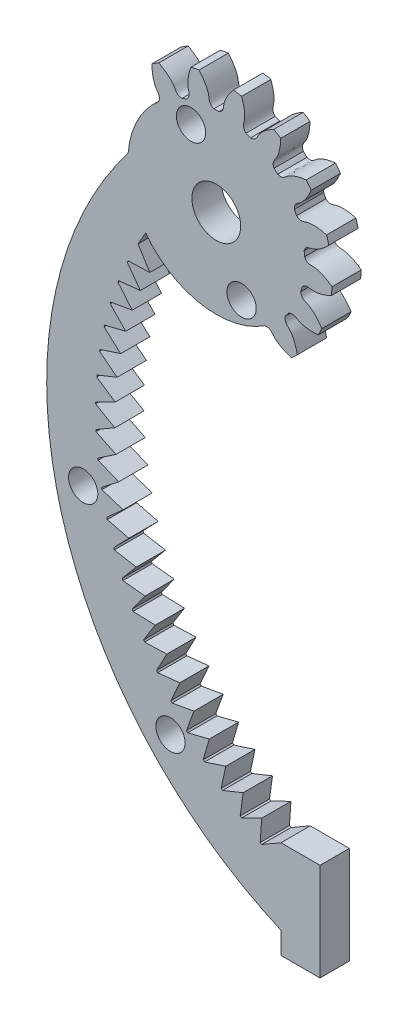
SolidWorks part; units mm, degrees
ref_plane "前视基准面" through (0, 0, 0) normal (0, 0, 1) x (1, 0, 0)
ref_plane "上视基准面" through (0, 0, 0) normal (0, 1, 0) x (1, 0, 0)
ref_plane "右视基准面" through (0, 0, 0) normal (1, 0, 0) x (0, 0, -1)
sketch "草图1" plane through (0, 0, 0) normal (0, 0, 1) x (1, 0, 0)
  circle A0 centre (0, 0) radius 11.875
extrude "凸台-拉伸1" add sketch "草图1" along normal blind 30
ref_axis "基准轴1" through (0, 0, -1.5) along (0, 0, 1)
sketch "草图2" plane through (0, 0, 0) normal (0, 0, 1) x (1, 0, 0)
  line L0 (0, 0) -> (0, 11.875) construction
  circle A0 centre (0, 0) radius 11.875 construction
  arc A1 (0.2521, 9.059) -> (-0.2521, 9.059) centre (0, 0) ccw
  arc A2 (3.8946, 13.4259) -> (-3.8946, 13.4259) centre (0, 0) ccw
  spline S0 degree 3 poles (0.2521, 9.059) (0.7848, 9.281) (0.7077, 9.6935) (0.7979, 10.081) (0.8062, 10.1139) (0.8163, 10.1505) (0.8282, 10.1907) (0.8421, 10.2345) (0.8582, 10.2818) (0.8766, 10.3324) (0.8974, 10.3865) (0.9208, 10.4438) (0.947, 10.5043) (0.976, 10.5679) (1.008, 10.6345) (1.0431, 10.704) (1.0815, 10.7763) (1.1232, 10.8513) (1.1685, 10.929) (1.2174, 11.0091) (1.27, 11.0916) (1.3265, 11.1763) (1.3869, 11.2632) (1.4514, 11.3521) (1.5201, 11.4429) (1.5931, 11.5354) (1.6704, 11.6295) (1.7522, 11.7251) (1.8386, 11.822) (1.9295, 11.9201) (2.0252, 12.0192) (2.1257, 12.1193) (2.2311, 12.22) (2.3414, 12.3213) (2.4567, 12.4231) (2.577, 12.5251) (2.7025, 12.6272) (2.8331, 12.7292) (2.969, 12.831) (3.1101, 12.9323) (3.2564, 13.0331) (3.4081, 13.1332) (3.6198, 13.2668) (3.7832, 13.3632) (3.8946, 13.4259) knots 0 0 0 0 0.193883 0.199024 0.204851 0.211363 0.21856 0.226443 0.235011 0.244265 0.254205 0.264829 0.27614 0.288136 0.300817 0.314184 0.328236 0.342973 0.358397 0.374505 0.391299 0.408779 0.426944 0.445795 0.465331 0.485552 0.506459 0.528051 0.550329 0.573293 0.596941 0.621276 0.646296 0.672001 0.698392 0.725468 0.753229 0.781677 0.810809 0.840627 0.871131 0.90232 0.934195 1 1 1 1
  spline S1 degree 3 poles (-0.2521, 9.059) (-0.7848, 9.281) (-0.7077, 9.6935) (-0.7979, 10.081) (-0.8062, 10.1139) (-0.8163, 10.1505) (-0.8282, 10.1907) (-0.8421, 10.2345) (-0.8582, 10.2818) (-0.8766, 10.3324) (-0.8974, 10.3865) (-0.9208, 10.4438) (-0.947, 10.5043) (-0.976, 10.5679) (-1.008, 10.6345) (-1.0431, 10.704) (-1.0815, 10.7763) (-1.1232, 10.8513) (-1.1685, 10.929) (-1.2174, 11.0091) (-1.27, 11.0916) (-1.3265, 11.1763) (-1.3869, 11.2632) (-1.4514, 11.3521) (-1.5201, 11.4429) (-1.5931, 11.5354) (-1.6704, 11.6295) (-1.7522, 11.7251) (-1.8386, 11.822) (-1.9295, 11.9201) (-2.0252, 12.0192) (-2.1257, 12.1193) (-2.2311, 12.22) (-2.3414, 12.3213) (-2.4567, 12.4231) (-2.577, 12.5251) (-2.7025, 12.6272) (-2.8331, 12.7292) (-2.969, 12.831) (-3.1101, 12.9323) (-3.2564, 13.0331) (-3.4081, 13.1332) (-3.6198, 13.2668) (-3.7832, 13.3632) (-3.8946, 13.4259) knots 0 0 0 0 0.193883 0.199024 0.204851 0.211363 0.21856 0.226443 0.235011 0.244265 0.254205 0.264829 0.27614 0.288136 0.300817 0.314184 0.328236 0.342973 0.358397 0.374505 0.391299 0.408779 0.426944 0.445795 0.465331 0.485552 0.506459 0.528051 0.550329 0.573293 0.596941 0.621276 0.646296 0.672001 0.698392 0.725468 0.753229 0.781677 0.810809 0.840627 0.871131 0.90232 0.934195 1 1 1 1
extrude "切除-拉伸1" cut sketch "草图2" along normal through all
pattern_circular "阵列(圆周)1" count 17 every 21.176 about axis through (0, 0, -1.5) along (0, 0, 1) of "切除-拉伸1"
sketch "草图3" plane through (0, 0, 0) normal (0, 0, 1) x (1, 0, 0)
  circle A0 centre (0, 0) radius 10.625 construction
  dimension "Dn" = 21.25
sketch "草图4" plane through (0, 0, 0) normal (0, 1, 0) x (1, 0, 0)
  line L1 (-19.5079, 27) -> (19.5079, 27)
  line L2 (-19.5079, 27) -> (-19.5079, -27)
  line L3 (-19.5079, -27) -> (19.5079, -27)
  line L4 (19.5079, 27) -> (19.5079, -27)
  line L5 (-19.5079, 27) -> (19.5079, -27) construction
  line L6 (-19.5079, -27) -> (19.5079, 27) construction
  point P0 (0, 0)
  dimension "D1" = 3
extrude "切除-拉伸2" cut sketch "草图4" against normal through all both and the other way through all
sketch "草图5" plane through (0, 0, 27) normal (0, 0, -1) x (-1, 0, 0)
  circle A1 centre (0, 0) radius 2.5
  circle A3 centre (-2.5889, -6.5037) radius 1.5
  circle A5 centre (2.5889, 6.5037) radius 1.5
extrude "切除-拉伸3" cut sketch "草图5" against normal blind 10
sketch "草图6" plane through (0, 0, 27) normal (0, 0, -1) x (-1, 0, 0)
  arc A0 (-4.5546, -7.8348) -> (6.2893, 6.5248) centre (0, 0) ccw
  arc A34 (-1.9124, -8.8584) -> (-1.4168, -8.9511) centre (0, 0) ccw
  arc A35 (-0.4197, -11.8676) -> (0.4197, -11.8676) centre (0, 0) ccw
  arc A36 (1.4168, -8.9511) -> (1.9124, -8.8584) centre (0, 0) ccw
  arc A37 (3.8958, -11.2178) -> (4.6784, -10.9146) centre (0, 0) ccw
  arc A38 (4.5546, -7.8348) -> (4.9833, -7.5694) centre (0, 0) ccw
  arc A39 (7.685, -9.053) -> (8.3053, -8.4875) centre (0, 0) ccw
  arc A40 (7.0773, -5.6605) -> (7.3812, -5.2581) centre (0, 0) ccw
  arc A41 (10.4364, -5.6655) -> (10.8105, -4.9142) centre (0, 0) ccw
  arc A42 (8.6442, -2.7216) -> (8.7822, -2.2366) centre (0, 0) ccw
  arc A43 (11.7782, -1.5129) -> (11.8557, -0.6771) centre (0, 0) ccw
  arc A44 (9.0436, 0.5848) -> (8.9971, 1.0869) centre (0, 0) ccw
  arc A45 (11.5294, 2.8441) -> (11.2997, 3.6513) centre (0, 0) ccw
  arc A46 (8.2217, 3.8123) -> (7.9969, 4.2636) centre (0, 0) ccw
  arc A47 (9.7234, 6.8169) -> (9.2176, 7.4867) centre (0, 0) ccw
  arc A48 (6.2893, 6.5248) -> (5.9167, 6.8645) centre (0, 0) ccw
  arc A49 (6.6043, 9.8691) -> (5.8907, 10.3109) centre (0, 0) ccw
  arc A50 (3.5076, 8.3562) -> (3.0374, 8.5383) centre (0, 0) ccw
  arc A51 (2.5932, 11.5884) -> (1.7682, 11.7426) centre (0, 0) ccw
  arc A52 (0.2521, 9.059) -> (-0.2521, 9.059) centre (0, 0) ccw
  arc A53 (-1.7682, 11.7426) -> (-2.5932, 11.5884) centre (0, 0) ccw
  arc A54 (-3.0374, 8.5383) -> (-3.5076, 8.3562) centre (0, 0) ccw
  arc A55 (-5.8907, 10.3109) -> (-6.6043, 9.8691) centre (0, 0) ccw
  arc A56 (-5.9167, 6.8645) -> (-6.2893, 6.5248) centre (0, 0) ccw
  arc A57 (-9.2176, 7.4867) -> (-9.7234, 6.8169) centre (0, 0) ccw
  arc A58 (-7.9969, 4.2636) -> (-8.2217, 3.8123) centre (0, 0) ccw
  arc A59 (-11.2997, 3.6513) -> (-11.5294, 2.8441) centre (0, 0) ccw
  arc A60 (-8.9971, 1.0869) -> (-9.0436, 0.5848) centre (0, 0) ccw
  arc A61 (-11.8557, -0.6771) -> (-11.7782, -1.5129) centre (0, 0) ccw
  arc A62 (-8.7822, -2.2366) -> (-8.6442, -2.7216) centre (0, 0) ccw
  arc A63 (-10.8105, -4.9142) -> (-10.4364, -5.6655) centre (0, 0) ccw
  arc A64 (-7.3812, -5.2581) -> (-7.0773, -5.6605) centre (0, 0) ccw
  arc A65 (-8.3053, -8.4875) -> (-7.685, -9.053) centre (0, 0) ccw
  arc A66 (-4.9833, -7.5694) -> (-4.5546, -7.8348) centre (0, 0) ccw
  arc A67 (-4.6784, -10.9146) -> (-3.8958, -11.2178) centre (0, 0) ccw
  arc A68 (-1.9124, -8.8584) -> (-1.4168, -8.9511) centre (0, 0) ccw
  arc A69 (-0.4197, -11.8676) -> (0.4197, -11.8676) centre (0, 0) ccw
  arc A70 (1.4168, -8.9511) -> (1.9124, -8.8584) centre (0, 0) ccw
  arc A71 (3.8958, -11.2178) -> (4.6784, -10.9146) centre (0, 0) ccw
  arc A72 (4.5546, -7.8348) -> (4.9833, -7.5694) centre (0, 0) ccw
  arc A73 (7.685, -9.053) -> (8.3053, -8.4875) centre (0, 0) ccw
  arc A74 (7.0773, -5.6605) -> (7.3812, -5.2581) centre (0, 0) ccw
  arc A75 (10.4364, -5.6655) -> (10.8105, -4.9142) centre (0, 0) ccw
  arc A76 (8.6442, -2.7216) -> (8.7822, -2.2366) centre (0, 0) ccw
  arc A77 (11.7782, -1.5129) -> (11.8557, -0.6771) centre (0, 0) ccw
  arc A78 (9.0436, 0.5848) -> (8.9971, 1.0869) centre (0, 0) ccw
  arc A79 (11.5294, 2.8441) -> (11.2997, 3.6513) centre (0, 0) ccw
  arc A80 (8.2217, 3.8123) -> (7.9969, 4.2636) centre (0, 0) ccw
  arc A81 (9.7234, 6.8169) -> (9.2176, 7.4867) centre (0, 0) ccw
  arc A101 (-4.6784, -10.9146) -> (-3.8958, -11.2178) centre (0, 0) ccw
  spline S34 degree 3 poles (4805.1572, -1377.7128) (-187.6631, 113.8798) (-25.4991, -30.4781) (-3.5148, -10.8956) (-3.3596, -10.7459) (-3.2216, -10.6015) (-3.1, -10.4638) (-2.994, -10.3337) (-2.903, -10.2123) (-2.8259, -10.1004) (-2.7618, -9.9992) (-2.7099, -9.9092) (-2.669, -9.8315) (-2.6418, -9.7744) (0.1965, -3.3034) (-48.5064, 24.9333) (4487.2668, -2209.3378) knots -14.565488 -14.565488 -14.565488 -14.565488 0.514448 0.554205 0.591221 0.625495 0.657027 0.685816 0.711864 0.735171 0.755735 0.773557 0.788637 0.800976 0.806117 4.426834 4.426834 4.426834 4.426834 only from (-3.8958, -11.2178) to (-1.9124, -8.8584)
  spline S35 degree 3 poles (-4982.3947, -439.1618) (54.2381, 5.7271) (-1.3765, -3.0093) (-1.0675, -10.0686) (-1.0628, -10.1317) (-1.0527, -10.219) (-1.0368, -10.3216) (-1.0137, -10.4392) (-0.9822, -10.5713) (-0.9411, -10.7174) (-0.8893, -10.877) (-0.8257, -11.0494) (-0.7491, -11.2338) (-0.6585, -11.4296) (12.7751, -37.6466) (216.3536, 38.4884) (-4978.3687, 450.8925) knots -3.426843 -3.426843 -3.426843 -3.426843 0.193883 0.199024 0.211363 0.226443 0.244265 0.264829 0.288136 0.314184 0.342973 0.374505 0.408779 0.445795 0.485552 15.57433 15.57433 15.57433 15.57433 only from (-1.4168, -8.9511) to (-0.4197, -11.8676)
  spline S36 degree 3 poles (4978.3629, 451.1441) (-216.1288, 38.398) (-12.7672, -37.6313) (0.6585, -11.4296) (0.7491, -11.2338) (0.8257, -11.0494) (0.8893, -10.877) (0.9411, -10.7174) (0.9822, -10.5713) (1.0137, -10.4392) (1.0368, -10.3216) (1.0527, -10.219) (1.0628, -10.1317) (1.0675, -10.0686) (1.3765, -3.0093) (-54.2378, 5.7271) (4982.3565, -439.1584) knots -14.565488 -14.565488 -14.565488 -14.565488 0.514448 0.554205 0.591221 0.625495 0.657027 0.685816 0.711864 0.735171 0.755735 0.773557 0.788637 0.800976 0.806117 4.426834 4.426834 4.426834 4.426834 only from (0.4197, -11.8676) to (1.4168, -8.9511)
  spline S37 degree 3 poles (-4487.3012, -2209.3547) (48.5067, 24.9335) (-0.1965, -3.3033) (2.6418, -9.7744) (2.669, -9.8315) (2.7099, -9.9092) (2.7618, -9.9992) (2.8259, -10.1004) (2.903, -10.2123) (2.994, -10.3337) (3.1, -10.4638) (3.2216, -10.6015) (3.3596, -10.7459) (3.5148, -10.8956) (25.5119, -30.4895) (187.8402, 114.0453) (-4805.0717, -1377.9495) knots -3.426843 -3.426843 -3.426843 -3.426843 0.193883 0.199024 0.211363 0.226443 0.244265 0.264829 0.288136 0.314184 0.342973 0.374505 0.408779 0.445795 0.485552 15.57433 15.57433 15.57433 15.57433 only from (1.9124, -8.8584) to (3.8958, -11.2178)
  spline S38 degree 3 poles (4479.2131, 2219.0715) (-215.4051, -42.2696) (1.6889, -39.7022) (4.7428, -10.4199) (4.7566, -10.2046) (4.7614, -10.005) (4.7585, -9.8213) (4.7492, -9.6538) (4.7346, -9.5027) (4.7163, -9.3681) (4.6954, -9.2501) (4.6732, -9.1486) (4.651, -9.0636) (4.6327, -9.0031) (2.3707, -2.3088) (-52.6441, -14.2526) (4804.5514, 1390.3317) knots -14.565488 -14.565488 -14.565488 -14.565488 0.514448 0.554205 0.591221 0.625495 0.657027 0.685816 0.711864 0.735171 0.755735 0.773557 0.788637 0.800976 0.806117 4.426834 4.426834 4.426834 4.426834 only from (4.6784, -10.9146) to (4.5546, -7.8348)
  spline S39 degree 3 poles (-3386.1727, -3681.1621) (36.2241, 40.7724) (1.0101, -3.1513) (5.9943, -8.16) (6.0403, -8.2034) (6.1065, -8.2612) (6.1874, -8.3262) (6.2837, -8.3976) (6.396, -8.474) (6.5248, -8.5543) (6.6706, -8.6374) (6.8337, -8.7219) (7.0146, -8.8066) (7.2135, -8.8902) (34.8032, -19.2147) (133.9578, 174.1998) (-3982.8232, -3020.6917) knots -3.426843 -3.426843 -3.426843 -3.426843 0.193883 0.199024 0.211363 0.226443 0.244265 0.264829 0.288136 0.314184 0.342973 0.374505 0.408779 0.445795 0.485552 15.57433 15.57433 15.57433 15.57433 only from (4.9833, -7.5694) to (7.685, -9.053)
  spline S40 degree 3 poles (3375.1208, 3687.3009) (-185.5897, -117.2285) (15.917, -36.4111) (8.1867, -8.003) (8.1218, -7.7973) (8.0541, -7.6093) (7.985, -7.4391) (7.9158, -7.2863) (7.8477, -7.1506) (7.7819, -7.0318) (7.7198, -6.9293) (7.6625, -6.8427) (7.6111, -6.7714) (7.5721, -6.7216) (3.0446, -1.2966) (-43.9406, -32.3074) (3977.865, 3032.0499) knots -14.565488 -14.565488 -14.565488 -14.565488 0.514448 0.554205 0.591221 0.625495 0.657027 0.685816 0.711864 0.735171 0.755735 0.773557 0.788637 0.800976 0.806117 4.426834 4.426834 4.426834 4.426834 only from (8.3053, -8.4875) to (7.0773, -5.6605)
  spline S41 degree 3 poles (-1827.7229, -4655.8081) (19.0493, 51.1048) (2.0802, -2.5736) (8.5372, -5.4436) (8.5958, -5.4675) (8.6784, -5.4974) (8.7774, -5.5288) (8.893, -5.5605) (9.0253, -5.5912) (9.1744, -5.6196) (9.3403, -5.6444) (9.523, -5.6643) (9.7222, -5.6779) (9.9378, -5.684) (39.3942, -5.3448) (61.9837, 210.8276) (-2622.6723, -4255.4728) knots -3.426843 -3.426843 -3.426843 -3.426843 0.193883 0.199024 0.211363 0.226443 0.244265 0.264829 0.288136 0.314184 0.342973 0.374505 0.408779 0.445795 0.485552 15.57433 15.57433 15.57433 15.57433 only from (7.3812, -5.2581) to (10.4364, -5.6655)
  spline S42 degree 3 poles (1815.1996, 4657.54) (-130.7094, -176.3551) (27.9953, -28.2024) (10.5249, -4.5052) (10.39, -4.3368) (10.2591, -4.186) (10.1331, -4.0522) (10.0134, -3.9347) (9.9008, -3.8328) (9.7966, -3.7458) (9.7017, -3.6727) (9.6169, -3.6126) (9.5433, -3.5647) (9.4889, -3.5324) (3.3074, -0.1092) (-29.3026, -45.9989) (2613.9459, 4264.2729) knots -14.565488 -14.565488 -14.565488 -14.565488 0.514448 0.554205 0.591221 0.625495 0.657027 0.685816 0.711864 0.735171 0.755735 0.773557 0.788637 0.800976 0.806117 4.426834 4.426834 4.426834 4.426834 only from (10.8105, -4.9142) to (8.6442, -2.7216)
  spline S43 degree 3 poles (-22.429, -5001.6614) (-0.6982, 54.5352) (2.8695, -1.6483) (9.9272, -1.992) (9.9904, -1.9931) (10.0783, -1.9911) (10.1819, -1.9847) (10.3011, -1.9725) (10.4356, -1.9534) (10.5849, -1.926) (10.7486, -1.8891) (10.9261, -1.8417) (11.1168, -1.7824) (11.3201, -1.7102) (38.6647, 9.247) (-18.3616, 218.982) (-908.315, -4915.5287) knots -3.426843 -3.426843 -3.426843 -3.426843 0.193883 0.199024 0.211363 0.226443 0.244265 0.264829 0.288136 0.314184 0.342973 0.374505 0.408779 0.445795 0.485552 15.57433 15.57433 15.57433 15.57433 only from (8.7822, -2.2366) to (11.7782, -1.5129)
  spline S44 degree 3 poles (10.1258, 4998.7524) (-58.1761, -211.6639) (36.2928, -16.1849) (11.4416, -0.3989) (11.255, -0.2906) (11.0784, -0.1973) (10.9127, -0.1181) (10.7586, -0.0518) (10.6168, 0.0026) (10.4882, 0.0461) (10.3733, 0.08) (10.2725, 0.1054) (10.1865, 0.1234) (10.1242, 0.134) (3.1235, 1.093) (-10.7071, -53.478) (896.9989, 4920.5822) knots -14.565488 -14.565488 -14.565488 -14.565488 0.514448 0.554205 0.591221 0.625495 0.657027 0.685816 0.711864 0.735171 0.755735 0.773557 0.788637 0.800976 0.806117 4.426834 4.426834 4.426834 4.426834 only from (11.8557, -0.6771) to (9.0436, 0.5848)
  spline S45 degree 3 poles (1785.8941, -4672.0127) (-20.3515, 50.6003) (3.2711, -0.5004) (9.9764, 1.7286) (10.0358, 1.7504) (10.117, 1.784) (10.2113, 1.8274) (10.3181, 1.8819) (10.4365, 1.9483) (10.5659, 2.0278) (10.7052, 2.1213) (10.8536, 2.2296) (11.01, 2.3538) (11.1735, 2.4945) (32.7134, 22.5899) (-96.2271, 197.5616) (928.7153, -4911.7153) knots -3.426843 -3.426843 -3.426843 -3.426843 0.193883 0.199024 0.211363 0.226443 0.244265 0.264829 0.288136 0.314184 0.342973 0.374505 0.408779 0.445795 0.485552 15.57433 15.57433 15.57433 15.57433 only from (8.9971, 1.0869) to (11.5294, 2.8441)
  spline S46 degree 3 poles (-1796.3157, 4664.8557) (22.2142, -218.3864) (39.6887, -1.9815) (10.8131, 3.7612) (10.6, 3.7948) (10.4016, 3.818) (10.2184, 3.832) (10.0508, 3.8382) (9.899, 3.8377) (9.7633, 3.8318) (9.6439, 3.8218) (9.5408, 3.8091) (9.4541, 3.7949) (9.3921, 3.7822) (2.5177, 2.1475) (9.3344, -53.7346) (-941.0928, 4912.3396) knots -14.565488 -14.565488 -14.565488 -14.565488 0.514448 0.554205 0.591221 0.625495 0.657027 0.685816 0.711864 0.735171 0.755735 0.773557 0.788637 0.800976 0.806117 4.426834 4.426834 4.426834 4.426834 only from (11.2997, 3.6513) to (8.2217, 3.8123)
  spline S47 degree 3 poles (3353.0223, -3711.3827) (-37.2561, 39.8316) (3.231, 0.715) (8.6783, 5.2158) (8.7257, 5.2576) (8.7894, 5.3182) (8.8616, 5.3928) (8.9415, 5.4821) (9.028, 5.5869) (9.1199, 5.7077) (9.216, 5.8452) (9.3152, 5.9998) (9.4162, 6.1721) (9.5178, 6.3624) (22.344, 32.8819) (-161.0966, 149.4595) (2640.3174, -4244.5474) knots -3.426843 -3.426843 -3.426843 -3.426843 0.193883 0.199024 0.211363 0.226443 0.244265 0.264829 0.288136 0.314184 0.342973 0.374505 0.408779 0.445795 0.485552 15.57433 15.57433 15.57433 15.57433 only from (7.9969, 4.2636) to (9.7234, 6.8169)
  spline S48 degree 3 poles (-3360.1547, 3700.9443) (99.6044, -195.6145) (37.7244, 12.4895) (8.7242, 7.4133) (8.5134, 7.3677) (8.32, 7.3177) (8.1441, 7.2646) (7.9856, 7.2097) (7.8442, 7.1544) (7.7198, 7.0999) (7.612, 7.0475) (7.5205, 6.9984) (7.4448, 6.9538) (7.3916, 6.9196) (1.5719, 2.912) (28.1153, -46.7341) (-2652.0846, 4240.6584) knots -14.565488 -14.565488 -14.565488 -14.565488 0.514448 0.554205 0.591221 0.625495 0.657027 0.685816 0.711864 0.735171 0.755735 0.773557 0.788637 0.800976 0.806117 4.426834 4.426834 4.426834 4.426834 only from (9.2176, 7.4867) to (6.2893, 6.5248)
  spline S49 degree 3 poles (895.5993, -449.7066) (-14.7361, 10.4752) (4.1652, 4.352) (6.2081, 7.9985) (6.2373, 8.0546) (6.2747, 8.1342) (6.3151, 8.2298) (6.3574, 8.342) (6.4001, 8.4709) (6.4422, 8.6167) (6.4821, 8.7797) (6.5188, 8.9597) (6.5507, 9.1569) (6.5767, 9.371) (8.0165, 27.1331) (-69.1734, 49.6198) (790.0464, -611.595) knots -1.94072 -1.94072 -1.94072 -1.94072 0.193883 0.199024 0.211363 0.226443 0.244265 0.264829 0.288136 0.314184 0.342973 0.374505 0.408779 0.445795 0.485552 9.582933 9.582933 9.582933 9.582933 only from (5.9167, 6.8645) to (6.6043, 9.8691)
  spline S50 degree 3 poles (-899.6353, 434.5997) (75.1884, -39.7336) (20.7059, 19.2647) (5.4571, 10.0643) (5.277, 9.9456) (5.1147, 9.8291) (4.9699, 9.716) (4.8419, 9.6076) (4.73, 9.505) (4.6337, 9.4092) (4.5521, 9.3214) (4.4845, 9.2426) (4.43, 9.1736) (4.3928, 9.1225) (2.0392, 5.6685) (15.9451, -8.5216) (-801.726, 601.2279) knots -8.57732 -8.57732 -8.57732 -8.57732 0.514448 0.554205 0.591221 0.625495 0.657027 0.685816 0.711864 0.735171 0.755735 0.773557 0.788637 0.800976 0.806117 2.940687 2.940687 2.940687 2.940687 only from (5.8907, 10.3109) to (3.5076, 8.3562)
  spline S51 degree 3 poles (997.5742, -95.8111) (-17.5251, 4.4446) (2.3118, 5.5628) (2.8995, 9.701) (2.9064, 9.7639) (2.9126, 9.8516) (2.9157, 9.9554) (2.9146, 10.0752) (2.9079, 10.2108) (2.8944, 10.362) (2.8728, 10.5284) (2.842, 10.7095) (2.8005, 10.9049) (2.7474, 11.114) (-2.3264, 28.1967) (-82.427, 21.2807) (957.63, -284.8976) knots -1.94072 -1.94072 -1.94072 -1.94072 0.193883 0.199024 0.211363 0.226443 0.244265 0.264829 0.288136 0.314184 0.342973 0.374505 0.408779 0.445795 0.485552 9.582933 9.582933 9.582933 9.582933 only from (3.0374, 8.5383) to (2.5932, 11.5884)
  spline S52 degree 3 poles (-995.8805, 80.2664) (84.4645, -9.8893) (12.3484, 25.4436) (1.4529, 11.356) (1.3279, 11.1802) (1.2187, 11.013) (1.1245, 10.8552) (1.0442, 10.7079) (0.977, 10.5718) (0.9218, 10.4477) (0.8775, 10.3364) (0.8429, 10.2384) (0.817, 10.1545) (0.8007, 10.0933) (-0.1462, 6.0223) (17.9467, -2.1861) (-964.7758, 271.0115) knots -8.57732 -8.57732 -8.57732 -8.57732 0.514448 0.554205 0.591221 0.625495 0.657027 0.685816 0.711864 0.735171 0.755735 0.773557 0.788637 0.800976 0.806117 2.940687 2.940687 2.940687 2.940687 only from (1.7682, 11.7426) to (0.2521, 9.059)
  spline S53 degree 3 poles (964.8212, 271.0241) (-17.9472, -2.1864) (0.1462, 6.0223) (-0.8007, 10.0933) (-0.817, 10.1545) (-0.8429, 10.2384) (-0.8775, 10.3364) (-0.9218, 10.4477) (-0.977, 10.5718) (-1.0442, 10.7079) (-1.1245, 10.8552) (-1.2187, 11.013) (-1.3279, 11.1802) (-1.4529, 11.356) (-12.3551, 25.4523) (-84.5484, -9.9324) (995.8802, 80.2767) knots -1.94072 -1.94072 -1.94072 -1.94072 0.193883 0.199024 0.211363 0.226443 0.244265 0.264829 0.288136 0.314184 0.342973 0.374505 0.408779 0.445795 0.485552 9.582933 9.582933 9.582933 9.582933 only from (-0.2521, 9.059) to (-1.7682, 11.7426)
  spline S54 degree 3 poles (-957.6265, -284.9073) (82.3333, 21.2906) (2.3233, 28.1863) (-2.7474, 11.114) (-2.8005, 10.9049) (-2.842, 10.7095) (-2.8728, 10.5284) (-2.8944, 10.362) (-2.9079, 10.2108) (-2.9146, 10.0752) (-2.9157, 9.9554) (-2.9126, 9.8516) (-2.9064, 9.7639) (-2.8995, 9.701) (-2.3118, 5.5629) (17.5245, 4.4446) (-997.5273, -95.8065) knots -8.57732 -8.57732 -8.57732 -8.57732 0.514448 0.554205 0.591221 0.625495 0.657027 0.685816 0.711864 0.735171 0.755735 0.773557 0.788637 0.800976 0.806117 2.940687 2.940687 2.940687 2.940687 only from (-2.5932, 11.5884) to (-3.0374, 8.5383)
  spline S55 degree 3 poles (801.7638, 601.2561) (-15.9455, -8.522) (-2.0392, 5.6684) (-4.3928, 9.1225) (-4.43, 9.1736) (-4.4845, 9.2426) (-4.5521, 9.3214) (-4.6337, 9.4092) (-4.73, 9.505) (-4.8419, 9.6076) (-4.9699, 9.716) (-5.1147, 9.8291) (-5.277, 9.9456) (-5.4571, 10.0643) (-20.7152, 19.2703) (-75.2511, -39.8041) (899.6314, 434.6092) knots -1.94072 -1.94072 -1.94072 -1.94072 0.193883 0.199024 0.211363 0.226443 0.244265 0.264829 0.288136 0.314184 0.342973 0.374505 0.408779 0.445795 0.485552 9.582933 9.582933 9.582933 9.582933 only from (-3.5076, 8.3562) to (-5.8907, 10.3109)
  spline S56 degree 3 poles (-790.0397, -611.6027) (69.0824, 49.5951) (-8.0157, 27.1222) (-6.5767, 9.371) (-6.5507, 9.1569) (-6.5188, 8.9597) (-6.4821, 8.7797) (-6.4422, 8.6167) (-6.4001, 8.4709) (-6.3574, 8.342) (-6.3151, 8.2298) (-6.2747, 8.1342) (-6.2373, 8.0546) (-6.2081, 7.9985) (-4.1653, 4.3521) (14.7355, 10.475) (-895.5572, -449.6853) knots -8.57732 -8.57732 -8.57732 -8.57732 0.514448 0.554205 0.591221 0.625495 0.657027 0.685816 0.711864 0.735171 0.755735 0.773557 0.788637 0.800976 0.806117 2.940687 2.940687 2.940687 2.940687 only from (-6.6043, 9.8691) to (-5.9167, 6.8645)
  spline S57 degree 3 poles (530.4237, 850.2851) (-11.7902, -13.7067) (-3.9491, 4.549) (-7.3916, 6.9196) (-7.4448, 6.9538) (-7.5205, 6.9984) (-7.612, 7.0475) (-7.7198, 7.0999) (-7.8442, 7.1544) (-7.9856, 7.2097) (-8.1441, 7.2646) (-8.32, 7.3177) (-8.5134, 7.3677) (-8.7242, 7.4133) (-26.2776, 10.4859) (-55.7906, -64.3) (681.8823, 730.2454) knots -1.94072 -1.94072 -1.94072 -1.94072 0.193883 0.199024 0.211363 0.226443 0.244265 0.264829 0.288136 0.314184 0.342973 0.374505 0.408779 0.445795 0.485552 9.582933 9.582933 9.582933 9.582933 only from (-6.2893, 6.5248) to (-9.2176, 7.4867)
  spline S58 degree 3 poles (-515.7537, -855.6978) (46.5016, 71.2015) (-17.272, 22.3951) (-9.5178, 6.3624) (-9.4162, 6.1721) (-9.3152, 5.9998) (-9.216, 5.8452) (-9.1199, 5.7077) (-9.028, 5.5869) (-8.9415, 5.4821) (-8.8616, 5.3928) (-8.7894, 5.3182) (-8.7257, 5.2576) (-8.6783, 5.2158) (-5.4561, 2.5535) (9.9565, 15.0908) (-672.6371, -742.8316) knots -8.57732 -8.57732 -8.57732 -8.57732 0.514448 0.554205 0.591221 0.625495 0.657027 0.685816 0.711864 0.735171 0.755735 0.773557 0.788637 0.800976 0.806117 2.940687 2.940687 2.940687 2.940687 only from (-9.7234, 6.8169) to (-7.9969, 4.2636)
  spline S59 degree 3 poles (187.447, 984.4784) (-6.0426, -17.0403) (-5.3258, 2.8152) (-9.3921, 3.7822) (-9.4541, 3.7949) (-9.5408, 3.8091) (-9.6439, 3.8218) (-9.7633, 3.8318) (-9.899, 3.8377) (-10.0508, 3.8382) (-10.2184, 3.832) (-10.4016, 3.818) (-10.6, 3.7948) (-10.8131, 3.7612) (-28.2911, 0.2852) (-28.7954, -80.1119) (372.0413, 927.2578) knots -1.94072 -1.94072 -1.94072 -1.94072 0.193883 0.199024 0.211363 0.226443 0.244265 0.264829 0.288136 0.314184 0.342973 0.374505 0.408779 0.445795 0.485552 9.582933 9.582933 9.582933 9.582933 only from (-8.2217, 3.8123) to (-11.2997, 3.6513)
  spline S60 degree 3 poles (-171.8123, -984.2262) (17.6405, 83.1917) (-24.1957, 14.6434) (-11.1735, 2.4945) (-11.01, 2.3538) (-10.8536, 2.2296) (-10.7052, 2.1213) (-10.5659, 2.0278) (-10.4365, 1.9483) (-10.3181, 1.8819) (-10.2113, 1.8274) (-10.117, 1.784) (-10.0358, 1.7504) (-9.9764, 1.7286) (-6.0101, 0.4101) (3.8327, 17.6684) (-358.8737, -935.6544) knots -8.57732 -8.57732 -8.57732 -8.57732 0.514448 0.554205 0.591221 0.625495 0.657027 0.685816 0.711864 0.735171 0.755735 0.773557 0.788637 0.800976 0.806117 2.940687 2.940687 2.940687 2.940687 only from (-11.5294, 2.8441) to (-8.9971, 1.0869)
  spline S61 degree 3 poles (-180.8455, 985.7124) (0.5211, -18.0724) (-5.9831, 0.7012) (-10.1242, 0.134) (-10.1865, 0.1234) (-10.2725, 0.1054) (-10.3733, 0.08) (-10.4882, 0.0461) (-10.6168, 0.0026) (-10.7586, -0.0518) (-10.9127, -0.1181) (-11.0784, -0.1973) (-11.255, -0.2906) (-11.4416, -0.3989) (-26.4837, -9.954) (2.0889, -85.1042) (11.954, 999.039) knots -1.94072 -1.94072 -1.94072 -1.94072 0.193883 0.199024 0.211363 0.226443 0.244265 0.264829 0.288136 0.314184 0.342973 0.374505 0.408779 0.445795 0.485552 9.582933 9.582933 9.582933 9.582933 only from (-9.0436, 0.5848) to (-11.8557, -0.6771)
  spline S62 degree 3 poles (195.3333, -979.8293) (-13.603, 83.9465) (-27.8517, 4.9141) (-11.3201, -1.7102) (-11.1168, -1.7824) (-10.9261, -1.8417) (-10.7486, -1.8891) (-10.5849, -1.926) (-10.4356, -1.9534) (-10.3011, -1.9725) (-10.1819, -1.9847) (-10.0783, -1.9911) (-9.9904, -1.9931) (-9.9272, -1.992) (-5.7524, -1.7887) (-2.8087, 17.8598) (3.3576, -1002.1119) knots -8.57732 -8.57732 -8.57732 -8.57732 0.514448 0.554205 0.591221 0.625495 0.657027 0.685816 0.711864 0.735171 0.755735 0.773557 0.788637 0.800976 0.806117 2.940687 2.940687 2.940687 2.940687 only from (-11.7782, -1.5129) to (-8.7822, -2.2366)
  spline S63 degree 3 poles (-524.7138, 853.8205) (7.0144, -16.6638) (-5.8324, -1.5074) (-9.4889, -3.5324) (-9.5433, -3.5647) (-9.6169, -3.6126) (-9.7017, -3.6727) (-9.7966, -3.7458) (-9.9008, -3.8328) (-10.0134, -3.9347) (-10.1331, -4.0522) (-10.2591, -4.186) (-10.39, -4.3368) (-10.5249, -4.5052) (-21.0995, -18.8488) (32.691, -78.6027) (-349.7478, 935.8944) knots -1.94072 -1.94072 -1.94072 -1.94072 0.193883 0.199024 0.211363 0.226443 0.244265 0.264829 0.288136 0.314184 0.342973 0.374505 0.408779 0.445795 0.485552 9.582933 9.582933 9.582933 9.582933 only from (-8.6442, -2.7216) to (-10.8105, -4.9142)
  spline S64 degree 3 poles (536.0981, -843.1011) (-43.0094, 73.3638) (-27.7461, -5.479) (-9.9378, -5.684) (-9.7222, -5.6779) (-9.523, -5.6643) (-9.3403, -5.6444) (-9.1744, -5.6196) (-9.0253, -5.5912) (-8.893, -5.5605) (-8.7774, -5.5288) (-8.6784, -5.4974) (-8.5958, -5.4675) (-8.5372, -5.4436) (-4.7178, -3.7459) (-9.0707, 15.6392) (365.1354, -933.2286) knots -8.57732 -8.57732 -8.57732 -8.57732 0.514448 0.554205 0.591221 0.625495 0.657027 0.685816 0.711864 0.735171 0.755735 0.773557 0.788637 0.800976 0.806117 2.940687 2.940687 2.940687 2.940687 only from (-10.4364, -5.6655) to (-7.3812, -5.2581)
  spline S65 degree 3 poles (-797.7166, 606.6154) (12.5604, -13.0046) (-4.894, -3.5126) (-7.5721, -6.7216) (-7.6111, -6.7714) (-7.6625, -6.8427) (-7.7198, -6.9293) (-7.7819, -7.0318) (-7.8477, -7.1506) (-7.9158, -7.2863) (-7.985, -7.4391) (-8.0541, -7.6093) (-8.1218, -7.7973) (-8.1867, -8.003) (-12.8657, -25.198) (58.878, -61.4855) (-664.2141, 746.3521) knots -1.94072 -1.94072 -1.94072 -1.94072 0.193883 0.199024 0.211363 0.226443 0.244265 0.264829 0.288136 0.314184 0.342973 0.374505 0.408779 0.445795 0.485552 9.582933 9.582933 9.582933 9.582933 only from (-7.0773, -5.6605) to (-8.3053, -8.4875)
  spline S66 degree 3 poles (804.4598, -592.5074) (-66.6071, 52.8729) (-23.8932, -15.132) (-7.2135, -8.8902) (-7.0146, -8.8066) (-6.8337, -8.7219) (-6.6706, -8.6374) (-6.5248, -8.5543) (-6.396, -8.474) (-6.2837, -8.3976) (-6.1874, -8.3262) (-6.1065, -8.2612) (-6.0403, -8.2034) (-5.9943, -8.16) (-3.0461, -5.1973) (-14.1077, 11.3064) (677.5997, -738.3076) knots -8.57732 -8.57732 -8.57732 -8.57732 0.514448 0.554205 0.591221 0.625495 0.657027 0.685816 0.711864 0.735171 0.755735 0.773557 0.788637 0.800976 0.806117 2.940687 2.940687 2.940687 2.940687 only from (-7.685, -9.053) to (-4.9833, -7.5694)
  spline S67 degree 3 poles (-4804.5882, 1390.3424) (52.6444, -14.2527) (-2.3707, -2.3088) (-4.6327, -9.0031) (-4.651, -9.0636) (-4.6732, -9.1486) (-4.6954, -9.2501) (-4.7163, -9.3681) (-4.7346, -9.5027) (-4.7492, -9.6538) (-4.7585, -9.8213) (-4.7614, -10.005) (-4.7566, -10.2046) (-4.7428, -10.4199) (-1.6871, -39.7193) (215.6474, -42.2666) (-4479.3094, 2218.839) knots -3.426843 -3.426843 -3.426843 -3.426843 0.193883 0.199024 0.211363 0.226443 0.244265 0.264829 0.288136 0.314184 0.342973 0.374505 0.408779 0.445795 0.485552 15.57433 15.57433 15.57433 15.57433 only from (-4.5546, -7.8348) to (-4.6784, -10.9146)
  spline S68 degree 3 poles (-3.8958, -11.2178) (-3.8242, -11.1617) (-3.6941, -11.0553) (-3.5148, -10.8956) (-3.3596, -10.7459) (-3.2216, -10.6015) (-3.1, -10.4638) (-2.994, -10.3337) (-2.903, -10.2123) (-2.8259, -10.1004) (-2.7618, -9.9992) (-2.7099, -9.9092) (-2.669, -9.8315) (-2.6418, -9.7744) (-2.4769, -9.3984) (-2.4769, -8.9788) (-1.9124, -8.8584) knots 0.467653 0.467653 0.467653 0.467653 0.514448 0.554205 0.591221 0.625495 0.657027 0.685816 0.711864 0.735171 0.755735 0.773557 0.788637 0.800976 0.806117 1 1 1 1
  spline S69 degree 3 poles (-1.4168, -8.9511) (-0.9339, -9.2672) (-1.0855, -9.6585) (-1.0675, -10.0686) (-1.0628, -10.1317) (-1.0527, -10.219) (-1.0368, -10.3216) (-1.0137, -10.4392) (-0.9822, -10.5713) (-0.9411, -10.7174) (-0.8893, -10.877) (-0.8257, -11.0494) (-0.7491, -11.2338) (-0.6585, -11.4296) (-0.549, -11.6432) (-0.4661, -11.7895) (-0.4197, -11.8676) knots 0 0 0 0 0.193883 0.199024 0.211363 0.226443 0.244265 0.264829 0.288136 0.314184 0.342973 0.374505 0.408779 0.445795 0.485552 0.532347 0.532347 0.532347 0.532347
  spline S70 degree 3 poles (0.4197, -11.8676) (0.4661, -11.7895) (0.549, -11.6432) (0.6585, -11.4296) (0.7491, -11.2338) (0.8257, -11.0494) (0.8893, -10.877) (0.9411, -10.7174) (0.9822, -10.5713) (1.0137, -10.4392) (1.0368, -10.3216) (1.0527, -10.219) (1.0628, -10.1317) (1.0675, -10.0686) (1.0855, -9.6585) (0.9339, -9.2672) (1.4168, -8.9511) knots 0.467653 0.467653 0.467653 0.467653 0.514448 0.554205 0.591221 0.625495 0.657027 0.685816 0.711864 0.735171 0.755735 0.773557 0.788637 0.800976 0.806117 1 1 1 1
  spline S71 degree 3 poles (1.9124, -8.8584) (2.4769, -8.9788) (2.4769, -9.3984) (2.6418, -9.7744) (2.669, -9.8315) (2.7099, -9.9092) (2.7618, -9.9992) (2.8259, -10.1004) (2.903, -10.2123) (2.994, -10.3337) (3.1, -10.4638) (3.2216, -10.6015) (3.3596, -10.7459) (3.5148, -10.8956) (3.6941, -11.0553) (3.8242, -11.1617) (3.8958, -11.2178) knots 0 0 0 0 0.193883 0.199024 0.211363 0.226443 0.244265 0.264829 0.288136 0.314184 0.342973 0.374505 0.408779 0.445795 0.485552 0.532347 0.532347 0.532347 0.532347
  spline S72 degree 3 poles (4.6784, -10.9146) (4.6935, -10.825) (4.718, -10.6586) (4.7428, -10.4199) (4.7566, -10.2046) (4.7614, -10.005) (4.7585, -9.8213) (4.7492, -9.6538) (4.7346, -9.5027) (4.7163, -9.3681) (4.6954, -9.2501) (4.6732, -9.1486) (4.651, -9.0636) (4.6327, -9.0031) (4.5012, -8.6142) (4.2185, -8.3041) (4.5546, -7.8348) knots 0.467653 0.467653 0.467653 0.467653 0.514448 0.554205 0.591221 0.625495 0.657027 0.685816 0.711864 0.735171 0.755735 0.773557 0.788637 0.800976 0.806117 1 1 1 1
  spline S73 degree 3 poles (4.9833, -7.5694) (5.5531, -7.4777) (5.7047, -7.869) (5.9943, -8.16) (6.0403, -8.2034) (6.1065, -8.2612) (6.1874, -8.3262) (6.2837, -8.3976) (6.396, -8.474) (6.5248, -8.5543) (6.6706, -8.6374) (6.8337, -8.7219) (7.0146, -8.8066) (7.2135, -8.8902) (7.4383, -8.9743) (7.5981, -9.0266) (7.685, -9.053) knots 0 0 0 0 0.193883 0.199024 0.211363 0.226443 0.244265 0.264829 0.288136 0.314184 0.342973 0.374505 0.408779 0.445795 0.485552 0.532347 0.532347 0.532347 0.532347
  spline S74 degree 3 poles (8.3053, -8.4875) (8.287, -8.3985) (8.2497, -8.2346) (8.1867, -8.003) (8.1218, -7.7973) (8.0541, -7.6093) (7.985, -7.4391) (7.9158, -7.2863) (7.8477, -7.1506) (7.7819, -7.0318) (7.7198, -6.9293) (7.6625, -6.8427) (7.6111, -6.7714) (7.5721, -6.7216) (7.3091, -6.4064) (6.9334, -6.2194) (7.0773, -5.6605) knots 0.467653 0.467653 0.467653 0.467653 0.514448 0.554205 0.591221 0.625495 0.657027 0.685816 0.711864 0.735171 0.755735 0.773557 0.788637 0.800976 0.806117 1 1 1 1
  spline S75 degree 3 poles (7.3812, -5.2581) (7.8794, -4.9667) (8.1621, -5.2769) (8.5372, -5.4436) (8.5958, -5.4675) (8.6784, -5.4974) (8.7774, -5.5288) (8.893, -5.5605) (9.0253, -5.5912) (9.1744, -5.6196) (9.3403, -5.6444) (9.523, -5.6643) (9.7222, -5.6779) (9.9378, -5.684) (10.1779, -5.6813) (10.3457, -5.6723) (10.4364, -5.6655) knots 0 0 0 0 0.193883 0.199024 0.211363 0.226443 0.244265 0.264829 0.288136 0.314184 0.342973 0.374505 0.408779 0.445795 0.485552 0.532347 0.532347 0.532347 0.532347
  spline S76 degree 3 poles (10.8105, -4.9142) (10.7613, -4.8378) (10.6673, -4.6984) (10.5249, -4.5052) (10.39, -4.3368) (10.2591, -4.186) (10.1331, -4.0522) (10.0134, -3.9347) (9.9008, -3.8328) (9.7966, -3.7458) (9.7017, -3.6727) (9.6169, -3.6126) (9.5433, -3.5647) (9.4889, -3.5324) (9.1298, -3.3335) (8.7119, -3.2948) (8.6442, -2.7216) knots 0.467653 0.467653 0.467653 0.467653 0.514448 0.554205 0.591221 0.625495 0.657027 0.685816 0.711864 0.735171 0.755735 0.773557 0.788637 0.800976 0.806117 1 1 1 1
  spline S77 degree 3 poles (8.7822, -2.2366) (9.1415, -1.785) (9.5172, -1.972) (9.9272, -1.992) (9.9904, -1.9931) (10.0783, -1.9911) (10.1819, -1.9847) (10.3011, -1.9725) (10.4356, -1.9534) (10.5849, -1.926) (10.7486, -1.8891) (10.9261, -1.8417) (11.1168, -1.7824) (11.3201, -1.7102) (11.5429, -1.621) (11.6962, -1.5519) (11.7782, -1.5129) knots 0 0 0 0 0.193883 0.199024 0.211363 0.226443 0.244265 0.264829 0.288136 0.314184 0.342973 0.374505 0.408779 0.445795 0.485552 0.532347 0.532347 0.532347 0.532347
  spline S78 degree 3 poles (11.8557, -0.6771) (11.7822, -0.6237) (11.6442, -0.5276) (11.4416, -0.3989) (11.255, -0.2906) (11.0784, -0.1973) (10.9127, -0.1181) (10.7586, -0.0518) (10.6168, 0.0026) (10.4882, 0.0461) (10.3733, 0.08) (10.2725, 0.1054) (10.1865, 0.1234) (10.1242, 0.134) (9.7175, 0.1897) (9.3139, 0.0748) (9.0436, 0.5848) knots 0.467653 0.467653 0.467653 0.467653 0.514448 0.554205 0.591221 0.625495 0.657027 0.685816 0.711864 0.735171 0.755735 0.773557 0.788637 0.800976 0.806117 1 1 1 1
  spline S79 degree 3 poles (8.9971, 1.0869) (9.169, 1.6378) (9.5869, 1.5991) (9.9764, 1.7286) (10.0358, 1.7504) (10.117, 1.784) (10.2113, 1.8274) (10.3181, 1.8819) (10.4365, 1.9483) (10.5659, 2.0278) (10.7052, 2.1213) (10.8536, 2.2296) (11.01, 2.3538) (11.1735, 2.4945) (11.349, 2.6583) (11.467, 2.778) (11.5294, 2.8441) knots 0 0 0 0 0.193883 0.199024 0.211363 0.226443 0.244265 0.264829 0.288136 0.314184 0.342973 0.374505 0.408779 0.445795 0.485552 0.532347 0.532347 0.532347 0.532347
  spline S80 degree 3 poles (11.2997, 3.6513) (11.2119, 3.6747) (11.0485, 3.7144) (10.8131, 3.7612) (10.6, 3.7948) (10.4016, 3.818) (10.2184, 3.832) (10.0508, 3.8382) (9.899, 3.8377) (9.7633, 3.8318) (9.6439, 3.8218) (9.5408, 3.8091) (9.4541, 3.7949) (9.3921, 3.7822) (8.9927, 3.6872) (8.6579, 3.4343) (8.2217, 3.8123) knots 0.467653 0.467653 0.467653 0.467653 0.514448 0.554205 0.591221 0.625495 0.657027 0.685816 0.711864 0.735171 0.755735 0.773557 0.788637 0.800976 0.806117 1 1 1 1
  spline S81 degree 3 poles (7.9969, 4.2636) (7.9582, 4.8395) (8.3618, 4.9543) (8.6783, 5.2158) (8.7257, 5.2576) (8.7894, 5.3182) (8.8616, 5.3928) (8.9415, 5.4821) (9.028, 5.5869) (9.1199, 5.7077) (9.216, 5.8452) (9.3152, 5.9998) (9.4162, 6.1721) (9.5178, 6.3624) (9.6223, 6.5785) (9.6891, 6.7328) (9.7234, 6.8169) knots 0 0 0 0 0.193883 0.199024 0.211363 0.226443 0.244265 0.264829 0.288136 0.314184 0.342973 0.374505 0.408779 0.445795 0.485552 0.532347 0.532347 0.532347 0.532347
  spline S82 degree 3 poles (9.2176, 7.4867) (9.1273, 7.4767) (8.9606, 7.4547) (8.7242, 7.4133) (8.5134, 7.3677) (8.32, 7.3177) (8.1441, 7.2646) (7.9856, 7.2097) (7.8442, 7.1544) (7.7198, 7.0999) (7.612, 7.0475) (7.5205, 6.9984) (7.4448, 6.9538) (7.3916, 6.9196) (7.0535, 6.6868) (6.8326, 6.33) (6.2893, 6.5248) knots 0.467653 0.467653 0.467653 0.467653 0.514448 0.554205 0.591221 0.625495 0.657027 0.685816 0.711864 0.735171 0.755735 0.773557 0.788637 0.800976 0.806117 1 1 1 1
  spline S101 degree 3 poles (-4.5546, -7.8348) (-4.2185, -8.3041) (-4.5012, -8.6142) (-4.6327, -9.0031) (-4.651, -9.0636) (-4.6732, -9.1486) (-4.6954, -9.2501) (-4.7163, -9.3681) (-4.7346, -9.5027) (-4.7492, -9.6538) (-4.7585, -9.8213) (-4.7614, -10.005) (-4.7566, -10.2046) (-4.7428, -10.4199) (-4.7179, -10.6586) (-4.6935, -10.825) (-4.6784, -10.9146) knots 0 0 0 0 0.193883 0.199024 0.211363 0.226443 0.244265 0.264829 0.288136 0.314184 0.342973 0.374505 0.408779 0.445795 0.485552 0.532347 0.532347 0.532347 0.532347
  dimension "D1" = 0
extrude "切除-拉伸4" cut sketch "草图6" against normal through all both and the other way through all contours A81 S82 A0 S81 | A79 S80 A0 S79 | A77 S78 A0 S77 | A75 S76 A0 S75 | A73 S74 A0 S73 | A71 S72 A0 S71 | A69 S70 A0 S69 | A0 S101 A101 S68 region at (3.669, -9.3609, 27) region at (0.8285, -9.1338, 27) region at (4.0721, -8.2178, 27) region at (3.7876, -10.6062, 27) region at (0.0397, -10.0542, 27) region at (-2.527, -8.8163, 27) region at (-0.2996, -11.2582, 27) region at (-3.595, -9.3896, 27) region at (-5.5412, -7.3082, 27) region at (-4.3463, -10.3897, 27) region at (-6.7441, -7.4569, 27) region at (-7.807, -4.813, 27) region at (-7.806, -8.1181, 27) region at (-8.9824, -4.5171, 27) region at (-9.0184, -1.6677, 27) region at (-10.2115, -4.75, 27) region at (-10.0076, -0.9672, 27) region at (-9.0119, 1.7027, 27) region at (-11.2378, -0.7404, 27) region at (-9.6813, 2.7133, 27) region at (-7.7883, 4.8432, 27) region at (-10.7465, 3.3691, 27) region at (-8.0474, 6.0273, 27) region at (-8.8037, 7.0237, 27)
sketch "草图8" plane through (0, 0, 27) normal (0, 0, -1) x (-1, 0, 0)
  line L0 (-6.625, -54.8537) -> (-6.625, -52.6196)
  line L1 (-6.625, -52.6196) -> (-10.625, -52.6196)
  line L2 (-10.625, -52.6196) -> (-10.625, -62.6196)
  line L3 (-10.625, -62.6196) -> (-6.625, -62.6196)
  line L4 (-6.625, -62.6196) -> (-6.625, -60.3855)
  line L5 (-6.0095, -57.6196) -> (-15.2405, -57.6196) construction
  line L6 (-10.625, 0) -> (-10.625, -67.3908) construction
  arc A0 (9.0336, 0.7237) -> (-6.625, -60.3855) centre (-22.625, -23.7249) cw
  arc A1 (-4.9833, -7.5694) -> (5.9167, 6.8645) centre (0, 0) ccw construction
  arc A2 (7.232, -5.4614) -> (-6.625, -54.8537) centre (-22.625, -23.7249) cw
  arc A3 (7.232, -5.4614) -> (9.0336, 0.7237) centre (0, 0) ccw
  point P15 (-10.625, -57.6196)
  dimension "D1" = 35
  dimension "D2" = 40
  dimension "D3" = 4
  dimension "D4" = 10
  dimension "D5" = 12
extrude "凸台-拉伸2" add sketch "草图8" against normal blind 3
sketch "草图9" plane through (0, 0, 27) normal (0, 0, -1) x (-1, 0, 0)
  line L0 (-6.625, -54.8537) -> (-6.625, -52.6196)
  line L1 (-6.625, -52.6196) -> (-10.625, -52.6196) construction
  line L2 (-6.625, -54.8537) -> (-6.625, -52.6196) construction
  line L3 (-6.625, -52.6196) -> (-4.6528, -53.7583)
  line L4 (-4.6484, -51.4331) -> (-2.6016, -52.4314)
  line L5 (-4.4925, -53.6618) -> (-4.6484, -51.4331)
  line L6 (-2.7593, -50.1117) -> (-0.6479, -50.9647)
  line L7 (-2.4484, -52.324) -> (-2.7593, -50.1117)
  line L8 (-0.9671, -48.6616) -> (1.1987, -49.3653)
  line L9 (-0.5026, -50.8469) -> (-0.9671, -48.6616)
  line L10 (0.7196, -47.0901) -> (2.9293, -47.641)
  line L11 (1.3354, -49.2376) -> (0.7196, -47.0901)
  line L12 (2.2926, -45.4047) -> (4.5353, -45.8002)
  line L13 (3.0567, -47.5041) -> (2.2926, -45.4047)
  line L14 (3.7443, -43.6138) -> (6.0091, -43.8518)
  line L15 (4.6529, -45.6547) -> (3.7443, -43.6138)
  line L16 (5.0674, -41.7259) -> (7.3433, -41.8054)
  line L17 (6.1162, -43.6985) -> (5.0674, -41.7259)
  line L18 (6.2556, -39.7503) -> (8.5315, -39.6708)
  line L19 (7.4395, -41.6449) -> (6.2556, -39.7503)
  line L20 (7.3031, -37.6967) -> (9.5679, -37.4586)
  line L21 (8.6163, -39.5041) -> (7.3031, -37.6967)
  line L22 (8.2049, -35.5749) -> (10.4475, -35.1795)
  line L23 (9.6409, -37.2864) -> (8.2049, -35.5749)
  line L24 (8.9564, -33.3955) -> (11.166, -32.8446)
  line L25 (10.5083, -35.0026) -> (8.9564, -33.3955)
  line L26 (9.554, -31.1689) -> (11.7198, -30.4652)
  line L27 (11.2143, -32.6638) -> (9.554, -31.1689)
  line L28 (9.9949, -28.9061) -> (12.1064, -28.053)
  line L29 (11.7554, -30.2815) -> (9.9949, -28.9061)
  line L30 (10.2769, -26.618) -> (12.3237, -25.6197)
  line L31 (12.129, -27.8673) -> (10.2769, -26.618)
  line L32 (10.3985, -24.3159) -> (12.3707, -23.1772)
  line L33 (12.3333, -25.4329) -> (10.3985, -24.3159)
  line L34 (10.3593, -22.0108) -> (12.2473, -20.7374)
  line L35 (12.3673, -22.9902) -> (10.3593, -22.0108)
  line L36 (10.1594, -19.7141) -> (11.9539, -18.3121)
  line L37 (12.2308, -20.551) -> (10.1594, -19.7141)
  line L38 (9.7998, -17.437) -> (11.4921, -15.9132)
  line L39 (11.9245, -18.1274) -> (9.7998, -17.437)
  line L40 (9.2821, -15.1905) -> (10.8641, -13.5523)
  line L41 (11.4499, -15.7309) -> (9.2821, -15.1905)
  line L42 (8.6091, -12.9855) -> (10.0729, -11.241)
  line L43 (10.8092, -13.3735) -> (8.6091, -12.9855)
  line L44 (7.7839, -10.8329) -> (9.1224, -8.9905)
  line L45 (10.0057, -11.0664) -> (7.7839, -10.8329)
  line L46 (6.8105, -8.7431) -> (8.0173, -6.8119)
  line L47 (9.0432, -8.8211) -> (6.8105, -8.7431)
  line L48 (-22.625, -23.7249) -> (-6.625, -52.6196) construction
  line L49 (-22.625, -23.7249) -> (-4.6484, -51.4331) construction
  arc A0 (-6.625, -54.8537) -> (7.232, -5.4614) centre (-22.625, -23.7249) ccw construction
  arc A1 (-6.625, -54.8537) -> (8.0173, -6.8119) centre (-22.625, -23.7249) ccw
  arc M7 (7.232, -5.4614) -> (-6.625, -54.8537) centre (-22.625, -23.7249) cw
  line M8 (-6.625, -54.8537) -> (-6.625, -52.6196)
  dimension "D1" = 60
  dimension "D3" = 4
  dimension "D2" = 23
extrude "凸台-拉伸4" add sketch "草图9" against normal blind 3 contours L3 M8 M7 | L5 L4 M7 | L7 L6 M7 | L9 L8 M7 | L11 L10 M7 | L13 L12 M7 | L15 L14 M7 | L17 L16 M7 | L19 L18 M7 | L21 L20 M7 | L25 L24 M7 | L23 L22 M7 | L27 L26 M7 | L29 L28 M7 | L31 L30 M7 | L33 L32 M7 | L35 L34 M7 | L37 L36 M7 | L39 L38 M7 | L41 L40 M7 | L43 L42 M7 | L45 L44 M7 | L47 L46 M7 region at (-7.9641, -8.1215, 27) region at (-8.978, -10.2933, 27) region at (-9.838, -12.5305, 27) region at (-10.5398, -14.8223, 27) region at (-11.08, -17.1575, 27) region at (-11.456, -19.5246, 27) region at (-11.666, -21.9122, 27) region at (-11.7089, -24.3086, 27) region at (-11.5846, -26.7022, 27) region at (-11.2936, -29.0813, 27) region at (-10.8373, -31.4343, 27) region at (-10.218, -33.7497, 27) region at (-9.4387, -36.0163, 27) region at (-8.5032, -38.223, 27) region at (-7.416, -40.3591, 27) region at (-6.1825, -42.4141, 27) region at (-4.8086, -44.3781, 27) region at (-3.3011, -46.2415, 27) region at (-1.6673, -47.9952, 27) region at (0.0849, -49.6306, 27) region at (1.9469, -51.1398, 27) region at (3.9096, -52.5154, 27) region at (5.9635, -53.7508, 27)
sketch "草图10" plane through (0, 0, 27) normal (0, 0, -1) x (-1, 0, 0)
  circle A2 centre (13.6383, -31.0701) radius 1.5
  circle A3 centre (4.6915, -48.6797) radius 1.5
extrude "切除-拉伸5" cut sketch "草图10" against normal through all
